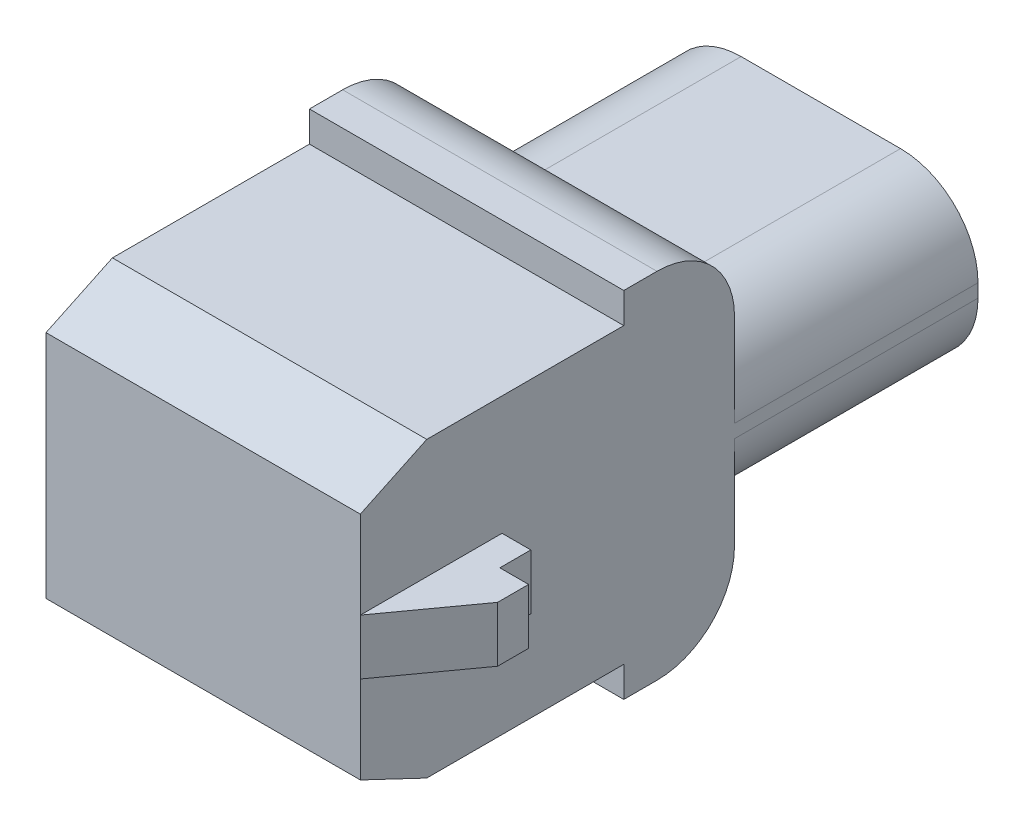
SolidWorks part; units mm, degrees
ref_plane "Front Plane" through (0, 0, 0) normal (0, 0, 1) x (1, 0, 0)
ref_plane "Top Plane" through (0, 0, 0) normal (0, 1, 0) x (1, 0, 0)
ref_plane "Right Plane" through (0, 0, 0) normal (1, 0, 0) x (0, 0, -1)
sketch "Sketch1" plane through (0, 0, 0) normal (1, 0, 0) x (0, 0, -1)
  line L0 (11, -3.8) -> (11, 3.8)
  line L1 (11, 3.8) -> (0, 3.8)
  line L2 (0, 3.8) -> (0, 8)
  line L3 (0, 8) -> (-5, 8)
  line L4 (-5, 8) -> (-5, 6.625)
  line L5 (-5, 6.625) -> (-13.9, 6.625)
  line L6 (-13.9, 6.625) -> (-16.9, 5.2)
  line L7 (-16.9, 5.2) -> (-16.9, -5.2)
  line L8 (-16.9, 0) -> (11, 0) construction
  line L9 (0, 3.8) -> (0, -3.8) construction
  line L10 (-13.9, -6.625) -> (-16.9, -5.2)
  line L11 (-5, -6.625) -> (-13.9, -6.625)
  line L12 (-5, -8) -> (-5, -6.625)
  line L13 (0, -8) -> (-5, -8)
  line L14 (0, -3.8) -> (0, -8)
  line L15 (11, -3.8) -> (0, -3.8)
  point P10 (-16.9, 1.6033)
  point P13 (0, 0)
  dimension "D1" = 11
  dimension "D2" = 27.9
  dimension "D3" = 6.625
  dimension "D4" = 5.2
  dimension "D5" = 3
  dimension "D6" = 5
  dimension "D7" = 8
  dimension "D8" = 3.8
extrude "Boss-Extrude1" add sketch "Sketch1" along normal blind 7.1 and the other way blind 7.1
fillet "Fillet1" radius 3.5 6 edges at (-7.1, 3.8, -5.5) (-7.1, -3.8, -5.5) (7.1, -3.8, -5.5) (7.1, 3.8, -5.5) (0, -8, 0) (0, 8, 0)
sketch "Sketch2" plane through (0, 0, 0) normal (0, 1, 0) x (1, 0, 0)
  line L0 (0, -17.5276) -> (0, -12.0545) construction
  line L1 (-7.1, -16.9) -> (-9.7, -13.3)
  line L2 (-9.7, -13.3) -> (-9.7, -11.9)
  line L3 (-9.7, -11.9) -> (-8.4, -11.9)
  line L4 (-8.4, -11.9) -> (-8.4, -10.5)
  line L5 (-8.4, -10.5) -> (-7.1, -10.5)
  line L6 (-7.1, -5) -> (-7.1, -13.9) construction
  line L7 (-7.1, -10.5) -> (-7.1, -16.9)
  line L8 (7.1, -10.5) -> (7.1, -16.9)
  line L9 (8.4, -10.5) -> (7.1, -10.5)
  line L10 (8.4, -11.9) -> (8.4, -10.5)
  line L11 (9.7, -11.9) -> (8.4, -11.9)
  line L12 (9.7, -13.3) -> (9.7, -11.9)
  line L13 (7.1, -16.9) -> (9.7, -13.3)
  dimension "D1" = 6.4
  dimension "D2" = 1.4
  dimension "D3" = 1.4
  dimension "D4" = 2.6
  dimension "D5" = 1.3
extrude "Boss-Extrude2" add sketch "Sketch2" along normal blind 1.25 and the other way blind 1.25
